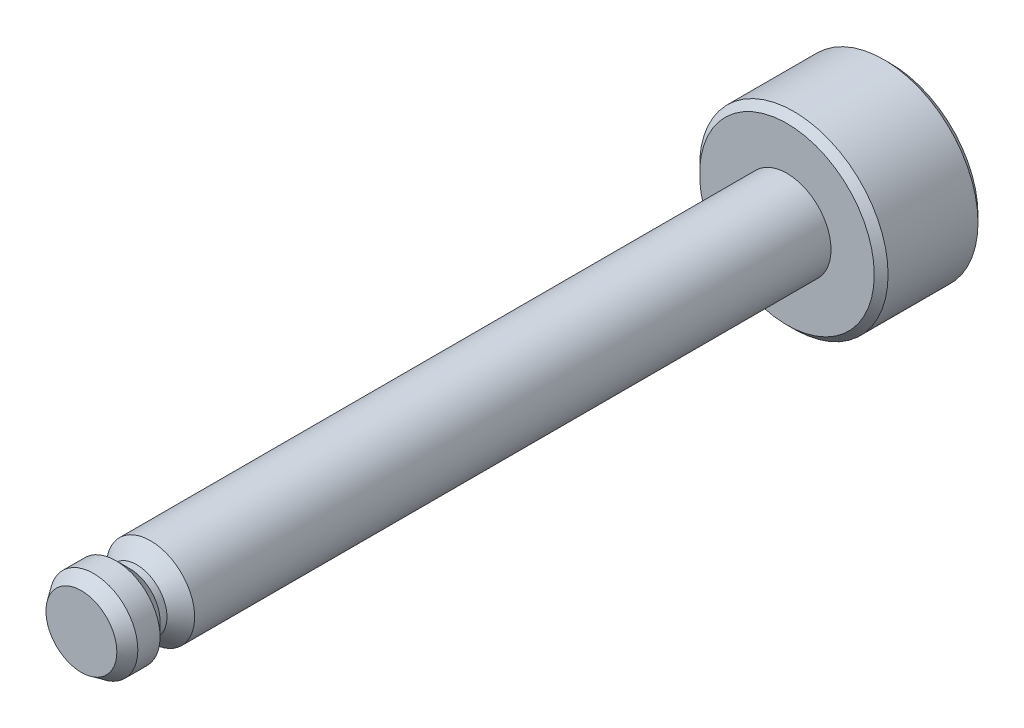
SolidWorks part; units mm, degrees
ref_plane "Front" through (0, 0, 0) normal (0, 0, 1) x (1, 0, 0)
ref_plane "Top" through (0, 0, 0) normal (0, 1, 0) x (1, 0, 0)
ref_plane "Right" through (0, 0, 0) normal (1, 0, 0) x (0, 0, -1)
sketch "Sketch2" plane through (0, 0, 0) normal (0, 0, 1) x (1, 0, 0)
  circle A0 centre (0, 0) radius 1.275
  dimension "D1" = 2.55
extrude "Shaft" add sketch "Sketch2" along normal blind 20.4
sketch "Sketch5" plane through (0, 0, 0) normal (0, 0, 1) x (1, 0, 0)
  circle A0 centre (0, 0) radius 2.725
  dimension "D1" = 5.45
extrude "Head" add sketch "Sketch5" against normal blind 3
chamfer "Chamfer1" distance 0.25 angle 55 1 edges at (1.275, 0, 20.4) first distance on face at (1.275, 0, 20.4)
chamfer "Deburs" distance 0.2 angle 45 2 edges at (2.725, 0, 0) (2.725, 0, -3)
sketch "Sketch6" plane through (0, 0, 0) normal (1, 0, 0) x (0, 0, -1)
  line L0 (0, 0) -> (-18.9, 0) construction
  line L1 (-18.9, 0) -> (-18.9, 0.875) construction
  line L2 (0, 1.275) -> (-20.043, 1.275) construction
  line L3 (-19.4, 1.275) -> (-18.4, 1.275)
  line L4 (-18.4, 1.275) -> (-18.8, 0.875)
  line L5 (-18.8, 0.875) -> (-19, 0.875)
  line L6 (-19, 0.875) -> (-19.4, 1.275)
  line L7 (-18.9, 0.875) -> (-18.9, 1.275) construction
  dimension "D1" = 18.9
  dimension "D2" = 0.4
  dimension "D3" = 1
revolve "e-Clip Notch Long" cut sketch "Sketch6" angle 360 about L0
equation "\"Length\"= 20mm"
equation "\"D1@Shaft\"=\"Length\"+.4mm"
equation "\"D1@Sketch6\"=\"Length\"-1.1mm"
equation "\"D1\"= 5.75mm - .3mm 'was: \"Countersink Diameter@Box Assy.Assembly\" - .3mm"
equation "\"D1@Sketch2\" = 2.55mm 'was: \"Plastic Hardware OD@Box Assy.Assembly\""
equation "\"D1@Head\" = 3mm 'was: \"Countersink Depth@Box Assy.Assembly\""
